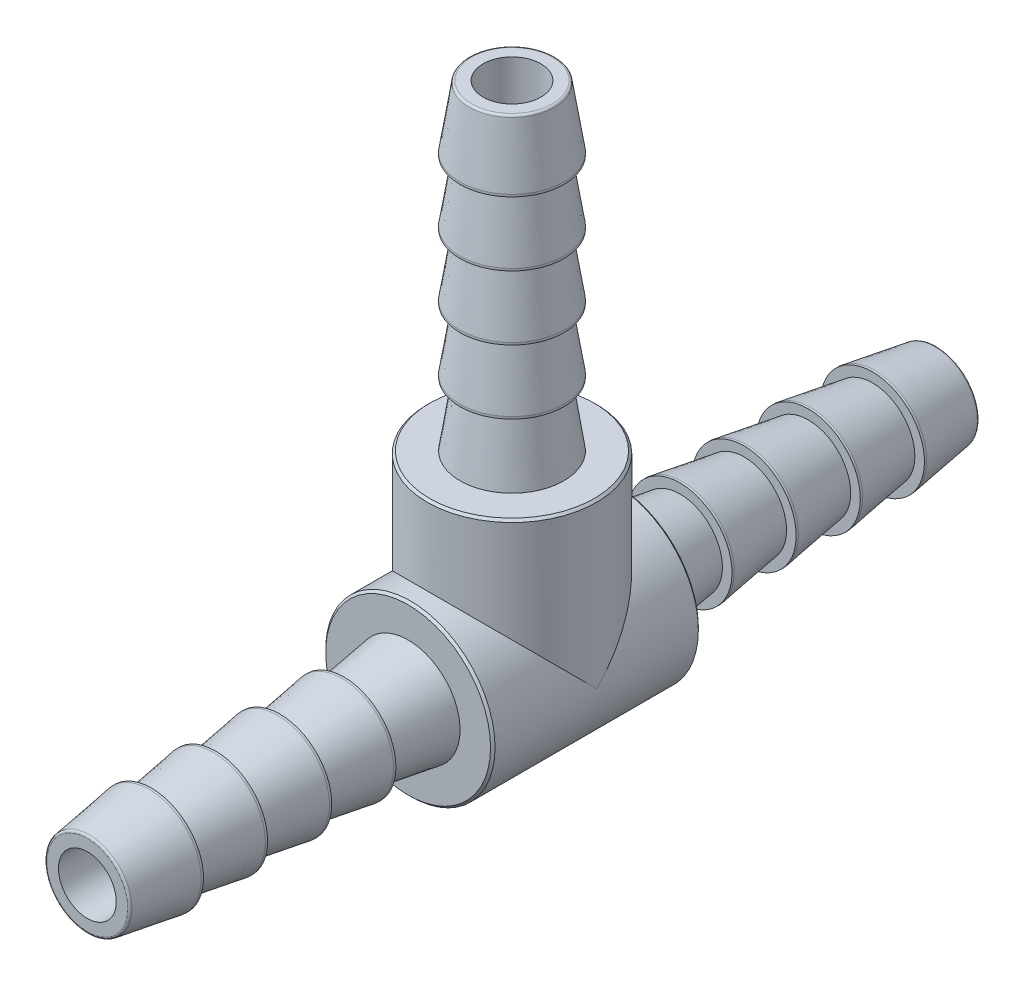
SolidWorks part; units mm, degrees
note: '?' marks a value the reader was unsure of.
ref_plane "Front Plane" through (0, 0, 0) normal (0, 0, 1) x (1, 0, 0)
ref_plane "Top Plane" through (0, 0, 0) normal (0, 1, 0) x (1, 0, 0)
ref_plane "Right Plane" through (0, 0, 0) normal (1, 0, 0) x (0, 0, -1)
sketch "Sketch1" plane through (0, 0, 0) normal (1, 0, 0) x (0, 0, -1)
  line L0 (-23.876, 0) -> (23.876, 0) construction
  line L2 (-1.6256, 27.2415) -> (1.6256, 27.2415) construction
  line L3 (-23.876, 2.3813) -> (-23.876, -2.3813) construction
  line L5 (0, 4.7625) -> (0, -4.7625) construction
  line L6 (-23.876, 1.6256) -> (-23.876, -1.6256) construction
  line L7 (-23.876, 2.921) -> (-23.876, -2.921) construction
  line L8 (-2.3813, 27.2415) -> (2.3813, 27.2415) construction
  line L10 (-2.921, 27.2415) -> (2.921, 27.2415) construction
  line L11 (-5.842, 4.7625) -> (-5.842, -4.7625) construction
  line L12 (-4.7625, 9.2075) -> (4.7625, 9.2075) construction
  line L13 (4.7625, 9.2075) -> (4.7625, -4.7625) construction
  line L14 (0, 0) -> (0, 27.2415) construction
  line L15 (-5.842, -4.7625) -> (4.7625, -4.7625) construction
  line L16 (23.876, 2.921) -> (23.876, -2.921) construction
  line L17 (23.876, 1.6256) -> (23.876, -1.6256) construction
  line L18 (23.876, 2.3813) -> (23.876, -2.3813) construction
  line L19 (5.842, 4.7625) -> (5.842, -4.7625) construction
  point P1 (-5.842, 0)
  point P32 (0, 9.2075)
sketch "Sketch2" plane through (0, 0, 0) normal (1, 0, 0) x (0, 0, -1)
  line L1 (-23.876, 0) -> (-23.876, 4.7625)
  line L2 (0, 0) -> (0, 4.7625) construction
  line L3 (-23.876, 4.7625) -> (23.876, 4.7625)
  line L5 (23.876, 0) -> (23.876, 4.7625)
  line L9 (-23.876, 0) -> (0, 0) construction
  line L12 (23.876, 0) -> (-23.876, 0)
revolve "Revolve1" add sketch "Sketch2" angle 360 about L9
sketch "Sketch3" plane through (0, 0, 0) normal (1, 0, 0) x (0, 0, -1)
  line L0 (-23.876, 4.7625) -> (-23.876, 2.3813)
  line L1 (-23.876, 4.7625) -> (-5.842, 4.7625)
  line L2 (-23.876, 2.3813) -> (-9.4488, 2.3813)
  line L3 (-23.876, 0) -> (0, 0) construction
  line L4 (-5.842, 4.7625) -> (-5.842, -4.7625) construction
  line L5 (-23.876, 2.921) -> (-23.876, -2.921) construction
  line L6 (-5.842, 2.921) -> (-9.4488, 2.3813)
  line L7 (0, 0) -> (0, 4.7625) construction
  line L12 (-5.842, 2.921) -> (-5.842, 4.7625)
  dimension "D1" = 3.6068
revolve "Cut-Revolve1" cut sketch "Sketch3" angle 360 about L3
sketch "Sketch4" plane through (0, 0, 0) normal (1, 0, 0) x (0, 0, -1)
  line L0 (-5.842, 0) -> (-23.876, 0) construction
  line L1 (-23.876, 2.3813) -> (-23.876, -2.3813) construction
  line L2 (-20.2692, 2.921) -> (-20.3962, 2.921)
  line L4 (-20.2692, 2.3813) -> (-20.2692, 2.921)
  line L5 (-20.3962, 2.921) -> (-23.876, 2.3813)
  line L7 (-20.2692, 2.3813) -> (-23.876, 2.3813)
  line L8 (-9.4488, 2.3813) -> (-23.876, 2.3813) construction
  dimension "D2" = 3.6068
  dimension "D1" = 0.127
revolve "Revolve2" add sketch "Sketch4" angle 360 about L0
pattern_linear "LPattern1" count 4 spacing 3.6068 along (0, 0, -1) of "Revolve2"
mirror "Mirror1" about plane through (0, 0, 0) normal (0, 0, 1) of "Cut-Revolve1", "Revolve2", "LPattern1"
sketch "Sketch6" plane through (0, 0, 0) normal (1, 0, 0) x (0, 0, -1)
  line L0 (0, 0) -> (0, 27.2415) construction
  line L1 (0, 0) -> (-4.7625, 0)
  line L2 (0, 0) -> (0, 27.2415)
  line L3 (0, 27.2415) -> (-4.7625, 27.2415)
  line L4 (-4.7625, 0) -> (-4.7625, 27.2415)
revolve "Revolve3" add sketch "Sketch6" angle 360 about L0
sketch "Sketch7" plane through (0, 0, 0) normal (1, 0, 0) x (0, 0, -1)
  line L0 (-2.921, 9.2075) -> (-2.3812, 12.8143)
  line L1 (-2.3813, 27.2415) -> (-4.7625, 27.2415)
  line L2 (-2.3813, 27.2415) -> (-2.3812, 12.8143)
  line L3 (-2.921, 9.2075) -> (-4.7625, 9.2075)
  line L4 (-4.7625, 27.2415) -> (-4.7625, 9.2075)
  line L5 (0, 0) -> (0, 27.2415) construction
  dimension "D1" = 3.6068
revolve "Cut-Revolve3" cut sketch "Sketch7" angle 360 about L5
sketch "Sketch8" plane through (0, 0, 0) normal (1, 0, 0) x (0, 0, -1)
  line L0 (-2.3813, 27.2415) -> (-2.921, 23.7617)
  line L1 (-2.921, 23.6347) -> (-2.3813, 23.6347)
  line L2 (-2.3813, 23.6347) -> (-2.3813, 27.2415)
  line L4 (0, 27.2415) -> (0, 0) construction
  line L5 (-1.6256, 27.2415) -> (1.6256, 27.2415) construction
  line L6 (-2.921, 23.7617) -> (-2.921, 23.6347)
  dimension "D2" = 3.6068
  dimension "D1" = 0.127
revolve "Revolve4" add sketch "Sketch8" angle 360 about L4
pattern_linear "LPattern2" count 4 spacing 3.6068 along (0, -1, 0) of "Revolve4"
sketch "Sketch5" plane through (0, 0, 0) normal (1, 0, 0) x (0, 0, -1)
  line L1 (-23.876, 1.6256) -> (33.2281, 1.6256)
  line L2 (-23.876, 1.6256) -> (-23.876, 0)
  line L3 (-23.876, 0) -> (33.2281, 0)
  line L5 (33.2281, 0) -> (33.2281, 1.6256)
revolve "Cut-Revolve2" cut sketch "Sketch5" angle 360 about L3
sketch "Sketch9" plane through (0, 0, 0) normal (1, 0, 0) x (0, 0, -1)
  line L0 (0, 27.2415) -> (0, 0) construction
  line L1 (-1.6256, 27.2415) -> (0, 27.2415)
  line L2 (-1.6256, 27.2415) -> (-1.6256, 0)
  line L3 (-1.6256, 0) -> (0, 0)
  line L4 (0, 27.2415) -> (0, 0)
revolve "Cut-Revolve4" cut sketch "Sketch9" angle 360 about L0
chamfer "Chamfer1" distance 0.127 angle 45 3 edges at (4.7625, 0, 5.842) (4.7625, 0, -5.842) (0, 9.2075, -4.7625)
fillet "Fillet1" radius 0.127 3 edges at (0, 2.3813, 23.876) (2.3813, 0, -23.876) (0, 27.2415, -2.3813)
ref_axis "Axis1" through (0, 0, -21.595) along (0, 0, 1)?
ref_axis "Axis2" through (0, 0, 0) along (0, 1, 0)?
ref_point "Point1"
ref_point "Point2"
ref_point "Point3"
equation "\"Barb End Length2@Sketch1\" = \"Barb End Length@Sketch1\""
equation "\"D2@Sketch4\" = \"Barb End Length@Sketch1\" /  ( \"No. of Barbs@LPattern1\" + 1 ) "
equation "\"D1@Sketch3\" = \"D2@Sketch4\""
equation "\"D3@LPattern1\" = \"D2@Sketch4\""
equation "\"No. of Barbs2@LPattern2\" = \"No. of Barbs@LPattern1\""
equation "\"D2@Sketch8\" = \"Barb End Length2@Sketch1\" /  ( \"No. of Barbs2@LPattern2\" + 1 ) "
equation "\"D1@Sketch7\" = \"D2@Sketch8\""
equation "\"D3@LPattern2\" = \"D2@Sketch8\""
